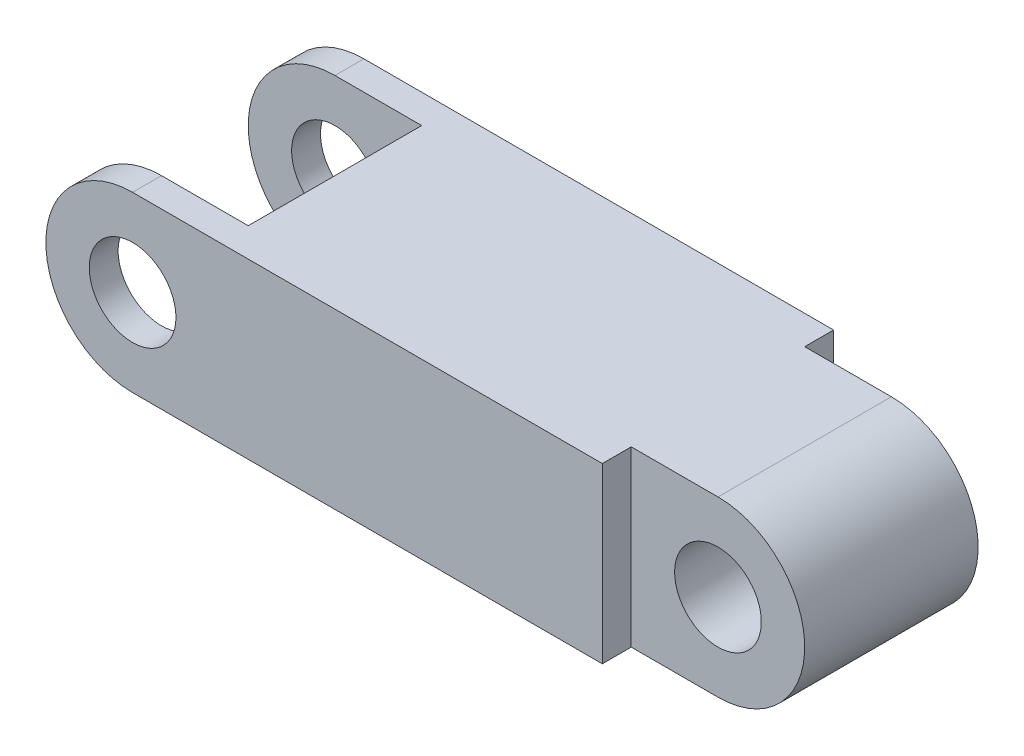
SolidWorks part; units mm, degrees
ref_plane "Front Plane" through (0, 0, 0) normal (0, 0, 1) x (1, 0, 0)
ref_plane "Top Plane" through (0, 0, 0) normal (0, 1, 0) x (1, 0, 0)
ref_plane "Right Plane" through (0, 0, 0) normal (1, 0, 0) x (0, 0, -1)
sketch "Sketch1" plane through (0, 0, 0) normal (0, 0, 1) x (1, 0, 0)
  line L0 (0, 0) -> (96.2421, 0) construction
  line L1 (0, 15) -> (96.2421, 15)
  line L2 (0, -15) -> (96.2421, -15)
  arc A0 (0, 15) -> (0, -15) centre (0, 0) ccw
  arc A1 (96.2421, -15) -> (96.2421, 15) centre (96.2421, 0) ccw
  circle A2 centre (0, 0) radius 7.5
  circle A3 centre (96.2421, 0) radius 7.5
  point P3 (48.121, 0)
  point P12 (96.2421, 0)
  dimension "D1" = 15
  dimension "D2" = 15
  dimension "D3" = 30
extrude "Boss-Extrude1" add sketch "Sketch1" along normal blind 40
sketch "Sketch2" plane through (0, 15, 0) normal (0, 1, 0) x (1, 0, 0)
  line L0 (-15, 0) -> (-15, -40) construction
  line L1 (15, -5) -> (-15, -5)
  line L2 (15, -5) -> (15, -35)
  line L3 (15, -35) -> (-15, -35)
  line L4 (-15, -5) -> (-15, -35)
  line L6 (0, -40) -> (0, 0) construction
  line L7 (111.2421, 0) -> (81.2421, 0)
  line L8 (111.2421, 0) -> (111.2421, -5)
  line L9 (111.2421, -5) -> (81.2421, -5)
  line L10 (81.2421, 0) -> (81.2421, -5)
  line L11 (111.2421, -40) -> (81.2421, -40)
  line L12 (111.2421, -40) -> (111.2421, -35)
  line L13 (111.2421, -35) -> (81.2421, -35)
  line L14 (81.2421, -40) -> (81.2421, -35)
  point P7 (-15, -20)
  point P10 (0, -20)
  dimension "D1" = 30
  dimension "D2" = 30
extrude "Cut-Extrude1" cut sketch "Sketch2" against normal through all
